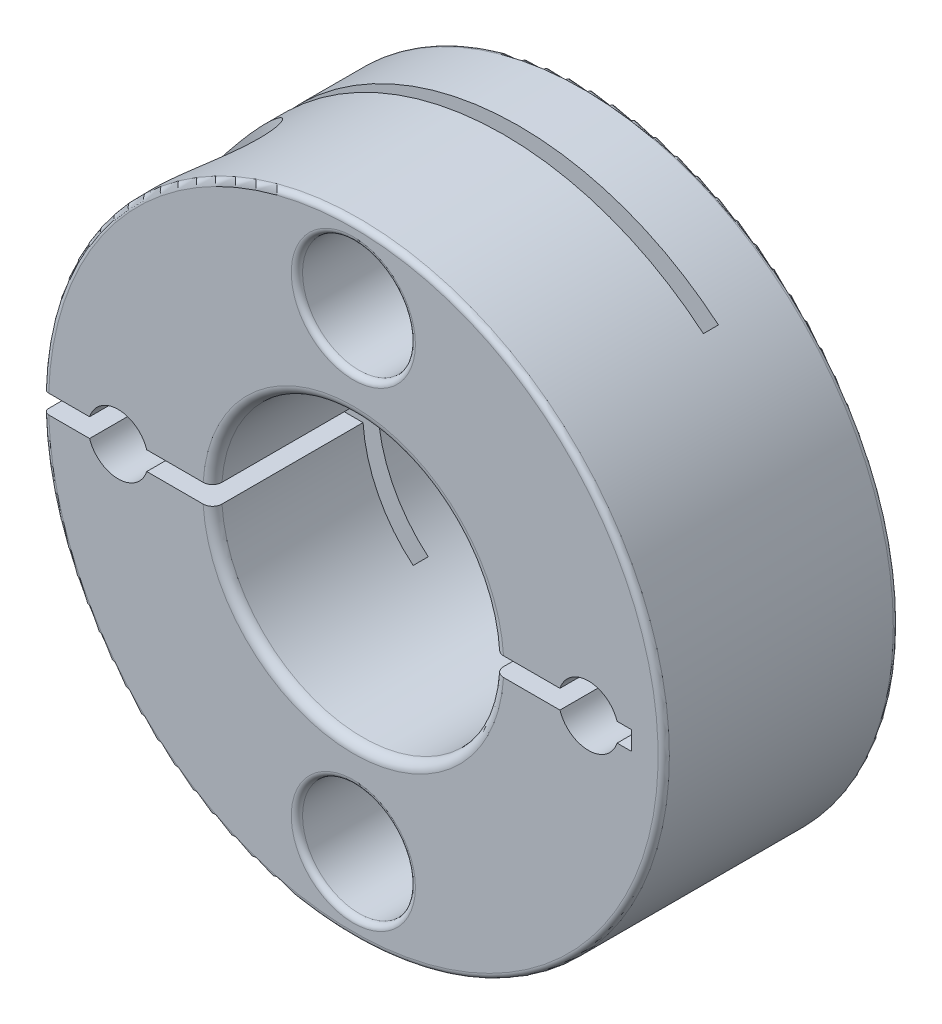
SolidWorks part; units mm, degrees
ref_plane "Front Plane" through (0, 0, 0) normal (0, 0, 1) x (1, 0, 0)
ref_plane "Top Plane" through (0, 0, 0) normal (0, 1, 0) x (1, 0, 0)
ref_plane "Right Plane" through (0, 0, 0) normal (1, 0, 0) x (0, 0, -1)
ref_axis "Axis_X" through (-6.6084, 0, 0) along (1, 0, 0)
ref_axis "Axis_Y" through (0, 6.6, 0) along (0, -1, 0)
ref_axis "Axis_Z" through (0, 0, -0.3894) along (0, 0, 1)
ref_plane "Dim.MSM_9" through (0, 0, 6) normal (0, 0, 1) x (1, 0, 0)
ref_plane "Dim.A" through (0, 0, 12) normal (0, 0, 1) x (1, 0, 0)
ref_plane "Dim.MSM_13" through (0, 0, 4) normal (0, 0, 1) x (1, 0, 0)
ref_plane "Dim.B_s_2" through (0, 0, 2) normal (0, 0, 1) x (1, 0, 0)
sketch "Sketch1" plane through (0, 0, 0) normal (0, 0, 1) x (1, 0, 0)
  circle A0 centre (0, 0) radius 16.5
  dimension "D" = 33
extrude "Boss-Extrude1" add sketch "Sketch1" along normal blind 12.5
ref_plane "Plane1" through (0, 0, 3.7) normal (0, 0, -1) x (-1, 0, 0)
sketch "Sketch2" plane through (0, 0, 3.7) normal (0, 0, -1) x (-1, 0, 0)
  line L0 (-10.606, 12.6397) -> (10.606, -12.6397)
  line L1 (0, 0) -> (0, 16.5) construction
  arc A0 (10.606, -12.6397) -> (-10.606, 12.6397) centre (0, 0) ccw
  dimension "D" = 33
  dimension "FIX_1" = 40
extrude "Cut-Extrude21" cut sketch "Sketch2" against normal blind 0.8
sketch "Sketch15" plane through (0, 0, 3.7) normal (0, 0, -1) x (-1, 0, 0)
  arc A0 (13.377, -9.6595) -> (1.1998, 16.4563) centre (0, 0) ccw
  arc A1 (1.1998, 16.4563) -> (13.377, -9.6595) centre (13.595, 6.339) ccw
  dimension "D" = 33
  dimension "MSM_63" = 16
  dimension "MSM_62" = 13.595
  dimension "MSM_61" = 6.339
extrude "Cut-Extrude22" [suppressed] cut sketch "Sketch15" against normal blind 0.8
sketch "Sketch4" plane through (0, 0, 12.5) normal (0, 0, 1) x (1, 0, 0)
  circle A0 centre (0, 0) radius 7.5
  dimension "D2_s" = 15
extrude "Cut-Extrude2" cut sketch "Sketch4" against normal through all
fillet "Fillet3" radius 0.5 2 edges at (7.5, 0, 0) (7.5, 0, 12.5)
sketch "Sketch3" plane through (0, 0, 0) normal (0, 1, 0) x (1, 0, 0)
  line L0 (0, 0) -> (0, -12.5) construction
  line L1 (-16.5, -12.5) -> (16.5, -12.5) construction
  line L2 (0, -4.5) -> (-16.5, -4.5)
  line L3 (-16.5, -4.5) -> (-16.5, -12.5)
  line L4 (-16.5, -12.5) -> (14.7819, -12.5)
  line L5 (6.6, -3.7) -> (-6.6, -3.7) construction
  line L6 (0, -4.5) -> (0, -7.5002)
  arc A0 (14.7819, -12.5) -> (0, -7.5002) centre (3.924, -20.25) ccw
  dimension "MSM_6" = 13.34
  dimension "D" = 33
  dimension "LF" = 12.5
  dimension "MSM_2" = 0.8
  dimension "MSM_4" = 3.924
  dimension "MSM_5" = 7.75
extrude "Cut-Extrude11" cut sketch "Sketch3" against normal mid plane 1
sketch "Sketch14" plane through (0, 0, 0) normal (0, 1, 0) x (1, 0, 0)
  line L0 (0, 0) -> (0, -12.5) construction
  line L3 (0, -4.5) -> (-16.5, -4.5)
  line L4 (-16.5, -4.5) -> (-16.5, -12.5)
  line L5 (-16.5, -12.5) -> (10.8579, -12.5)
  line L6 (6.6, -3.7) -> (-6.6, -3.7) construction
  line L8 (0, -4.5) -> (0, -6.91)
  arc A0 (10.8579, -12.5) -> (0, -6.91) centre (0, -20.25) ccw
  dimension "MSM_6" = 13.34
  dimension "MSM_2" = 0.8
  dimension "D" = 33
  dimension "LF" = 12.5
  dimension "MSM_5" = 7.75
extrude "Cut-Extrude12" [suppressed] cut sketch "Sketch14" against normal mid plane 1
sketch "Sketch5" plane through (0, 0, 0) normal (0, 0, -1) x (-1, 0, 0)
  circle A0 centre (0, 12.5) radius 3
  circle A1 centre (0, -12.5) radius 3
  circle A2 centre (0, 0) radius 12.5 construction
  dimension "MSM_8" = 25
  dimension "KSS_1" = 6
extrude "Cut-Extrude4" cut sketch "Sketch5" against normal through all
hole_wizard "Tap1" positions "Sketch6" profile "Sketch7" hole size "M1.6x0.35" standard "JIS"
sketch "Sketch6" plane through (0, 0, 0) normal (0, 0, -1) x (-1, 0, 0)
  circle A0 centre (0, 0) radius 12.5 construction
  point P0 (-12.5, 0)
  point P2 (12.5, 0)
  dimension "MSM_8" = 25
sketch "Sketch7" plane through (12.5, 0, 0) normal (1, 0, 0) x (0, 1, 0)
  line L0 (0, 0) -> (0, 4.7388)
  line L1 (0, 4.7388) -> (1.2295, 4)
  line L2 (1.2295, 4) -> (1.2295, 0)
  line L5 (1.2295, 0) -> (0, 0)
  line L10 (0, 4.7388) -> (-1.2295, 4) construction
  line L11 (0, -6.35) -> (0, 107.95) construction
  dimension "HSD_1" = 2.459
  dimension "HSL_1" = 4
  dimension "Drill Angle" = 118
cosmetic thread "Thread1" parameters "MSM_10"=3
cosmetic thread "Thread2" parameters "MSM_10"=3
sketch "Sketch8" plane through (0, 0, 0) normal (0, 0, -1) x (-1, 0, 0)
  circle A0 centre (0, 12.5) radius 3.25
  circle A1 centre (0, -12.5) radius 3.25
  dimension "MSM_11" = 6.5
extrude "Cut-Extrude23" [suppressed] cut sketch "Sketch8" against normal blind 4
ref_plane "Plane2" through (0, 4, 0) normal (0, 1, 0) x (1, 0, 0)
sketch "Sketch9" plane through (0, 4, 0) normal (0, 1, 0) x (1, 0, 0)
  line L2 (-16.4924, -12.5) -> (16.5, -12.5) construction
  circle A0 centre (-12, -8.5) radius 3
  dimension "MSM_14" = 6
  dimension "F" = 4
  dimension "KSS_2" = 12
extrude "Cut-Extrude6" cut sketch "Sketch9" along normal through all
sketch "Sketch11" plane through (0, 4, 0) normal (0, 1, 0) x (1, 0, 0)
  circle A0 centre (-12, -8.5) radius 1.6
  dimension "MSM_15" = 3.2
extrude "Cut-Extrude7" cut sketch "Sketch11" against normal blind 4.5
hole_wizard "Tap2" positions "Sketch12" profile "Sketch13" hole size "M1.6x0.35" standard "JIS" end condition through all
sketch "Sketch12" plane through (0, 0, 0) normal (0, 1, 0) x (1, 0, 0)
  point P0 (-12, -8.5)
sketch "Sketch13" plane through (-12, 0, 8.5) normal (1, 0, 0) x (0, 0, 1)
  line L0 (0, 0) -> (0, 16.5)
  line L1 (0, 16.5) -> (1.2295, 16.5)
  line L2 (1.2295, 16.5) -> (1.2295, 0)
  line L5 (1.2295, 0) -> (0, 0)
  line L11 (0, -6.35) -> (0, 107.95) construction
  dimension "HSD_2" = 2.459
  dimension "Thru Hole Depth" = 16.5
cosmetic thread "Thread3" parameters "MSM_17"=3
fillet "Fillet1" radius 0.3 2 edges at (-3, -12.5, 12.5) (-3, 12.5, 12.5)
fillet "Fillet2" radius 0.3 2 edges at (16.5, 0, 0) (16.5, 0, 12.5)
fillet "Fillet4" radius 0.1 1 edges at (-12, 4, 10.1)
ref_plane "Plane3" through (0, 0, 4) normal (0, 0, 1) x (1, 0, 0)
sketch "Sketch16" plane through (0, 0, 4) normal (0, 0, -1) x (-1, 0, 0)
  circle A0 centre (12.5, 0) radius 1.6
  circle A1 centre (-12.5, 0) radius 1.6
  dimension "MSM_64" = 3.2
extrude "Cut-Extrude24" cut sketch "Sketch16" against normal through all
sketch "Sketch18" plane through (0, 0, 0) normal (0, 0, 1) x (1, 0, 0)
  line L0 (0, 0) -> (-4.8, 0) construction
  circle A0 centre (0, 12.5) radius 2.4
  circle A1 centre (0, -12.5) radius 2.4
  dimension "FIX_91" = 4.8
  dimension "FIX_92" = 4.8
  dimension "MSM_8" = 25
extrude "Cut-Extrude25" [suppressed] cut sketch "Sketch18" along normal blind 5
sketch "Sketch17" [suppressed] plane through (0, 0, 0) normal (0, 0, 1) x (1, 0, 0)
  line L0 (0, 1.5) -> (0, 0) construction
  line L1 (0, 0) -> (1.7678, -1.7678) construction
  line L2 (0.0835, -1.4977) -> (1.0607, -2.4749)
  line L3 (1.0607, -2.4749) -> (2.4749, -1.0607)
  line L4 (2.4749, -1.0607) -> (1.4977, -0.0835)
  arc A0 (1.4977, -0.0835) -> (0.0835, -1.4977) centre (0, 0) ccw
  dimension "D2_s" = 15
  dimension "FIX_2" = 135
  dimension "B_s_2" = 2
  dimension "T_s_2" = 1
extrude "Cut-Extrude1" [suppressed] cut sketch "Sketch17" along normal through all
equation "\"Factor\"= 1.082532"
equation "\"KSS_1\"= IIF ( ( \"D\" = 26 and \"D2_s\" = 14 ) , 3 , \"MSM_9\" )"
equation "\"Cut-Extrude25\"= IIF ( ( \"D\" = 26 and \"D2_s\" = 14 ) , \"unsuppressed\" , \"suppressed\" )"
equation "\"KSS_2\"= IIF ( ( \"D\" = 26 and \"D2_s\" = 14 ) , 9 , \"A\" )"
equation "\"KSS_3\"= IIF ( ( \"D\" = 26 and \"D2_s\" = 14 ) , 4 , IIF ( ( \"D\" = 26 and \"D2_s\" = 13 ) , 4 , \"MSM_13\" ) )"
equation "\"T_s_2\"= IIF ( \"B_s_2\" = 12 , 3.3 , IIF ( \"B_s_2\" = 10 , 3.3 , IIF ( \"B_s_2\" = 8 , 3.3 , IIF ( \"B_s_2\" = 6 , 2.8 , IIF ( \"B_s_2\" = 5 , 2.3 , IIF ( \"B_s_2\" = 4 , 1.8 , IIF ( \"B_s_2\" = 3 , 1.4 , IIF ( \"B_s_2\" = 2 , 1 , 1 ) ) ) ) ) ) ) )"
